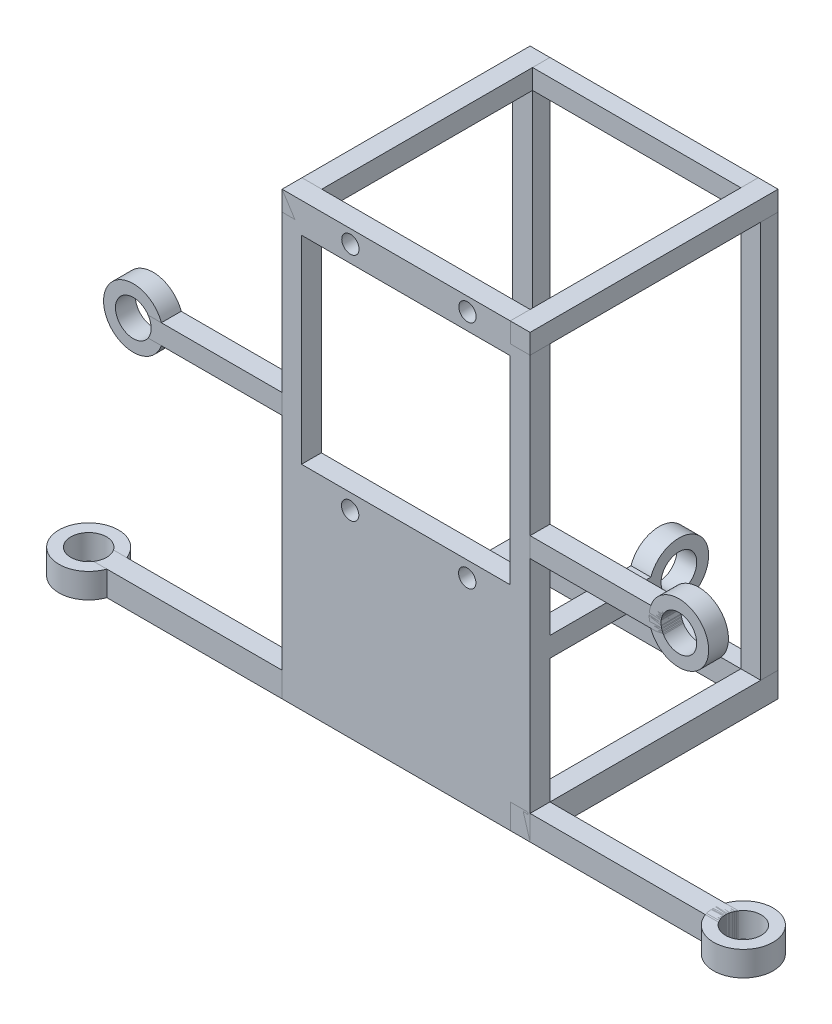
SolidWorks part; units mm, degrees
ref_plane "Front Plane" through (0, 0, 0) normal (0, 0, 1) x (1, 0, 0)
ref_plane "Top Plane" through (0, 0, 0) normal (0, 1, 0) x (1, 0, 0)
ref_plane "Right Plane" through (0, 0, 0) normal (1, 0, 0) x (0, 0, -1)
sketch "Sketch114" plane through (0, 0, 0) normal (1, 0, 0) x (0, 0, -1)
  line L1 (0, 0) -> (3.5, 0)
  line L2 (0, 0) -> (0, 80)
  line L3 (0, 80) -> (3.5, 80)
  line L4 (3.5, 0) -> (3.5, 80)
extrude "Boss-Extrude2" add sketch "Sketch114" along normal blind 4
sketch "Sketch115" plane through (0, 80, 0) normal (0, 1, 0) x (1, 0, 0)
  line L1 (0, 0) -> (50, 0)
  line L2 (0, 0) -> (0, 3.5)
  line L3 (0, 3.5) -> (50, 3.5)
  line L4 (50, 0) -> (50, 3.5)
extrude "Boss-Extrude3" add sketch "Sketch115" along normal blind 4 separate body
sketch "Sketch116" plane through (50, 0, 0) normal (1, 0, 0) x (0, 0, -1)
  line L1 (3.5, 80) -> (0, 80)
  line L2 (3.5, 80) -> (3.5, 0)
  line L3 (3.5, 0) -> (0, 0)
  line L4 (0, 80) -> (0, 0)
extrude "Boss-Extrude5" add sketch "Sketch116" against normal blind 4 separate body
sketch "Sketch117" plane through (0, 0, 0) normal (0, -1, 0) x (1, 0, 0)
  line L0 (0, 0) -> (0, -3.5) construction
  line L1 (0, -3.5) -> (50, -3.5)
  line L2 (0, -3.5) -> (0, 0)
  line L3 (0, 0) -> (50, 0)
  line L4 (50, -3.5) -> (50, 0)
extrude "Boss-Extrude6" add sketch "Sketch117" along normal blind 5 separate body contours L3 L4 L1 L2
sketch "Sketch119" plane through (50, 0, 0) normal (1, 0, 0) x (0, 0, -1)
  line L1 (3.5, -5) -> (-46.5, -5)
  line L2 (3.5, -5) -> (3.5, 0)
  line L3 (3.5, 0) -> (-46.5, 0)
  line L4 (-46.5, -5) -> (-46.5, 0)
  line L5 (3.5, 84) -> (-46.5, 84)
  line L6 (3.5, 84) -> (3.5, 80)
  line L7 (3.5, 80) -> (-46.5, 80)
  line L8 (-46.5, 84) -> (-46.5, 80)
extrude "Boss-Extrude7" add sketch "Sketch119" against normal blind 4 separate body
sketch "Sketch122" plane through (0, 0, 0) normal (-1, 0, 0) x (0, 0, 1)
  line L1 (-3.5, 84) -> (46.5, 84)
  line L2 (-3.5, 84) -> (-3.5, 80)
  line L3 (-3.5, 80) -> (46.5, 80)
  line L4 (46.5, 84) -> (46.5, 80)
  line L5 (-3.5, -5) -> (46.5, -5)
  line L6 (-3.5, -5) -> (-3.5, 0)
  line L7 (-3.5, 0) -> (46.5, 0)
  line L8 (46.5, -5) -> (46.5, 0)
extrude "Boss-Extrude8" add sketch "Sketch122" against normal blind 4 separate body
sketch "Sketch134" plane through (0, 0, 46.5) normal (0, 0, 1) x (1, 0, 0)
  line L1 (0, -5) -> (50, -5)
  line L2 (0, -5) -> (0, 84)
  line L3 (0, 84) -> (50, 84)
  line L4 (50, -5) -> (50, 84)
  point P6 (-65.4744, 70.3213)
extrude "Boss-Extrude18" add sketch "Sketch134" against normal blind 4 separate body
sketch "Sketch135" plane through (0, -5, 0) normal (0, -1, 0) x (-1, 0, 0)
  line L1 (-46, -46.5) -> (-91, -46.5)
  line L2 (-46, -46.5) -> (-46, -42.5)
  line L3 (-46, -42.5) -> (-91, -42.5)
  line L4 (-91, -46.5) -> (-91, -42.5)
extrude "Boss-Extrude19" add sketch "Sketch135" against normal blind 5 separate body
sketch "Sketch136" plane through (0, -5, 0) normal (0, -1, 0) x (1, 0, 0)
  line L1 (4, 46.5) -> (-41, 46.5)
  line L2 (4, 46.5) -> (4, 42.5)
  line L3 (4, 42.5) -> (-41, 42.5)
  line L4 (-41, 46.5) -> (-41, 42.5)
extrude "Boss-Extrude21" add sketch "Sketch136" against normal blind 5 separate body
sketch "Sketch137" plane through (0, -5, 0) normal (0, -1, 0) x (1, 0, 0)
  line L0 (91, 42.5) -> (91, 46.5) construction
  circle A0 centre (91, 44.5) radius 6
extrude "Boss-Extrude22" add sketch "Sketch137" against normal blind 5 separate body
sketch "Sketch139" plane through (0, -5, 0) normal (0, -1, 0) x (-1, 0, 0)
  line L0 (-91, -42.5) -> (-91, -46.5) construction
  circle A0 centre (-91, -44.5) radius 3.6
extrude "Cut-Extrude1" cut sketch "Sketch139" against normal blind 38 and the other way blind 10
sketch "Sketch140" plane through (0, -5, 0) normal (0, -1, 0) x (1, 0, 0)
  line L0 (-41, 46.5) -> (-41, 42.5) construction
  circle A0 centre (-41, 44.5) radius 6
extrude "Boss-Extrude23" add sketch "Sketch140" against normal blind 5 separate body
sketch "Sketch143" plane through (0, -5, 0) normal (0, -1, 0) x (1, 0, 0)
  circle A0 centre (-41, 44.5) radius 3.6
extrude "Cut-Extrude2" cut sketch "Sketch143" against normal blind 17 and the other way blind 29
sketch "Sketch145" plane through (0, 5, 42.5) normal (0, 0, -1) x (-1, 0, 0)
  line L1 (0, 39.5) -> (30, 39.5)
  line L2 (0, 39.5) -> (0, 43.5)
  line L3 (0, 43.5) -> (30, 43.5)
  line L4 (30, 39.5) -> (30, 43.5)
extrude "Boss-Extrude26" add sketch "Sketch145" against normal blind 4 separate body contours L4 L3 L2 L1
sketch "Sketch146" plane through (0, 5, 46.5) normal (0, 0, 1) x (1, 0, 0)
  line L0 (-30, 39.5) -> (-30, 43.5) construction
  circle A0 centre (-30, 41.5) radius 6
extrude "Boss-Extrude27" add sketch "Sketch146" against normal blind 4 separate body
sketch "Sketch147" plane through (0, 5, 46.5) normal (0, 0, 1) x (1, 0, 0)
  circle A0 centre (-30, 41.5) radius 3.6
extrude "Cut-Extrude3" cut sketch "Sketch147" against normal blind 21 and the other way blind 11
sketch "Sketch148" plane through (0, 5, 46.5) normal (0, 0, 1) x (1, 0, 0)
  line L1 (50, 39.5) -> (80, 39.5)
  line L2 (50, 39.5) -> (50, 43.5)
  line L3 (50, 43.5) -> (80, 43.5)
  line L4 (80, 39.5) -> (80, 43.5)
extrude "Boss-Extrude28" add sketch "Sketch148" against normal blind 4 separate body
sketch "Sketch149" plane through (0, 5, 42.5) normal (0, 0, -1) x (-1, 0, 0)
  line L0 (-80, 39.5) -> (-80, 43.5) construction
  circle A0 centre (-80, 41.5) radius 6
extrude "Boss-Extrude29" add sketch "Sketch149" against normal blind 4 separate body
sketch "Sketch150" plane through (0, 5, 46.5) normal (0, 0, 1) x (1, 0, 0)
  line L0 (80, 39.5) -> (80, 43.5) construction
  circle A0 centre (80, 41.5) radius 3.6
extrude "Cut-Extrude4" cut sketch "Sketch150" along normal blind 12 and the other way blind 14
sketch "Sketch155" plane through (0, 0, 42.5) normal (0, 0, -1) x (-1, 0, 0)
sketch "Sketch156" plane through (0, 0, 46.5) normal (0, 0, 1) x (1, 0, 0)
  line L1 (3.9148, 77.9202) -> (45.9148, 77.9202)
  line L2 (3.9148, 77.9202) -> (3.9148, -0.0798)
  line L3 (3.9148, -0.0798) -> (45.9148, -0.0798)
  line L4 (45.9148, 77.9202) -> (45.9148, -0.0798)
extrude "Cut-Extrude8" cut sketch "Sketch156" against normal blind 4
sketch "Sketch159" plane through (50, 0, 0) normal (1, 0, 0) x (0, 0, -1)
  line L0 (-46.5, -5) -> (-46.5, 84) construction
  line L1 (-46.5, 29.085) -> (-16.5, 29.085)
  line L2 (-46.5, 29.085) -> (-46.5, 25.085)
  line L3 (-46.5, 25.085) -> (-16.5, 25.085)
  line L4 (-16.5, 29.085) -> (-16.5, 25.085)
extrude "Boss-Extrude31" add sketch "Sketch159" against normal blind 4
sketch "Sketch160" plane through (46, 0, 0) normal (-1, 0, 0) x (0, 0, 1)
  line L0 (16.5, 25.085) -> (16.5, 29.085) construction
  circle A0 centre (16.5, 27.085) radius 6
extrude "Boss-Extrude32" add sketch "Sketch160" against normal blind 4
sketch "Sketch161" plane through (50, 0, 0) normal (1, 0, 0) x (0, 0, -1)
  circle A0 centre (-16.5, 27.085) radius 3.6
extrude "Cut-Extrude10" cut sketch "Sketch161" against normal blind 4
sketch "Sketch162" plane through (0, 0, 46.5) normal (0, 0, 1) x (1, 0, 0)
  line L1 (3.9148, 37.9202) -> (45.9148, 37.9202)
  line L2 (3.9148, 37.9202) -> (3.9148, -4.8929)
  line L7 (3.9148, -4.8929) -> (45.9148, -4.8929)
  line L8 (3.9148, 77.9202) -> (3.9148, -0.0798) construction
  line L13 (45.9148, -0.0798) -> (45.9148, 77.9202) construction
  line L14 (45.9148, 37.9202) -> (45.9148, -4.8929)
  line L15 (45.9148, 77.9202) -> (3.9148, 77.9202) construction
  dimension "D1" = 40
extrude "Boss-Extrude34" add sketch "Sketch162" against normal blind 4
sketch "Sketch163" plane through (0, 0, 46.5) normal (0, 0, 1) x (1, 0, 0)
sketch "Sketch164" plane through (0, 0, 42.5) normal (0, 0, -1) x (-1, 0, 0)
  circle A0 centre (-13.7714, 81.2786) radius 1.75
  circle A1 centre (-37.3714, 81.2786) radius 1.75
  circle A2 centre (-37.3214, 34.7786) radius 1.75
  circle A3 centre (-13.7214, 34.7786) radius 1.75
  point P6 (-37.3214, 29.7476)
  point P7 (0, 0)
  point P8 (-37.3214, 29.5916)
  point P9 (-13.7714, 29.5916)
  point P10 (-13.7714, 34.7786)
  point P13 (-37.3214, 34.7786)
  point P14 (0, 0)
  point P15 (0, 0)
  dimension "D1" = 23.6
sketch "Sketch165" plane through (0, 37.9202, 0) normal (0, 1, 0) x (1, 0, 0)
extrude "Cut-Extrude12" cut sketch "Sketch164" against normal blind 4
sketch "Sketch166" plane through (0, 31.9202, 0) normal (0, -1, 0) x (1, 0, 0)
